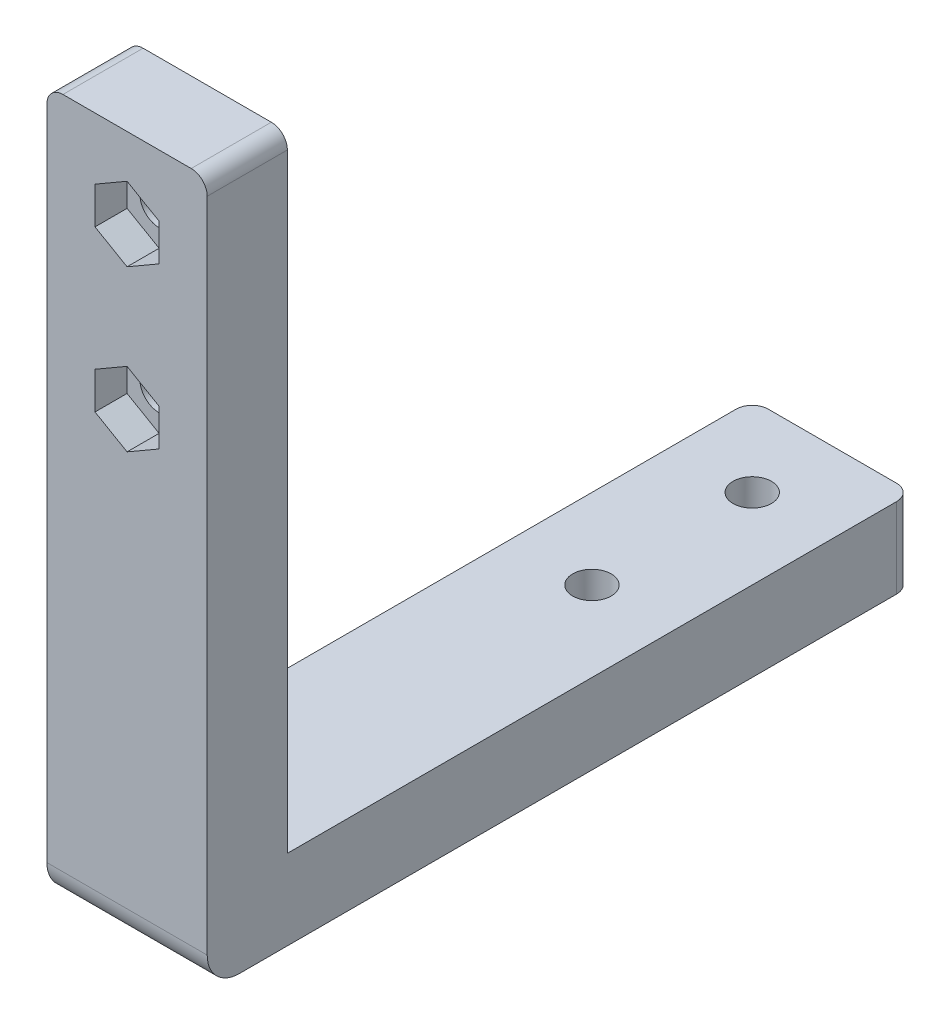
SolidWorks part; units mm, degrees
material "PEI"
ref_plane "Спереди" through (0, 0, 0) normal (0, 0, 1) x (1, 0, 0)
ref_plane "Сверху" through (0, 0, 0) normal (0, 1, 0) x (1, 0, 0)
ref_plane "Справа" through (0, 0, 0) normal (1, 0, 0) x (0, 0, -1)
sketch "Эскиз1" plane through (0, 0, 0) normal (1, 0, 0) x (0, 0, -1)
  line L0 (0, 44) -> (0, 0)
  line L1 (0, 0) -> (44, 0)
  line L2 (44, 0) -> (44, 5)
  line L3 (44, 5) -> (5, 5)
  line L4 (5, 5) -> (5, 44)
  line L5 (5, 44) -> (0, 44)
  dimension "D1" = 44
  dimension "D2" = 44
  dimension "D3" = 5
extrude "Бобышка-Вытянуть1" add sketch "Эскиз1" along normal blind 5 and the other way blind 5
sketch "Эскиз2" plane through (0, 5, 0) normal (0, 1, 0) x (1, 0, 0)
  line L1 (-10.7235, 34) -> (49989.2765, 34) construction
  line L2 (-5, 0) -> (5, 0) construction
  circle A0 centre (0, 39) radius 1.2
  circle A1 centre (0, 29) radius 1.2
  dimension "D1" = 2.4
  dimension "D2" = 29
  dimension "D3" = 5
extrude "Вырез-Вытянуть1" cut sketch "Эскиз2" against normal through all
sketch "Эскиз3" plane through (0, 0, -5) normal (0, 0, -1) x (-1, 0, 0)
  line L1 (13.3016, 34) -> (-49986.6984, 34) construction
  line L2 (5, 0) -> (-5, 0) construction
  circle A0 centre (0, 39) radius 1.2
  circle A1 centre (0, 29) radius 1.2
  dimension "D1" = 2.4
  dimension "D2" = 29
  dimension "D3" = 5
extrude "Вырез-Вытянуть2" cut sketch "Эскиз3" against normal through all
fillet "Скругление1" radius 1 4 edges at (-5, 2.5, -44) (5, 2.5, -44) (5, 44, -2.5) (-5, 44, -2.5)
fillet "Скругление2" radius 2 1 edges at (0, 0, 0)
sketch "Sketch1" plane through (0, 0, 0) normal (0, 0, -1) x (-1, 0, 0)
  line L0 (-0.2139, 34) -> (49999.7861, 34) construction
  line L1 (2, 27.8453) -> (0, 26.6906)
  line L2 (0, 41.3094) -> (-2, 40.1547)
  line L3 (-2, 40.1547) -> (-2, 37.8453)
  line L4 (-2, 37.8453) -> (0, 36.6906)
  line L5 (0, 36.6906) -> (2, 37.8453)
  line L6 (2, 37.8453) -> (2, 40.1547)
  line L7 (2, 40.1547) -> (0, 41.3094)
  line L8 (2, 30.1547) -> (2, 27.8453)
  line L9 (0, 31.3094) -> (2, 30.1547)
  line L10 (-2, 30.1547) -> (0, 31.3094)
  line L11 (-2, 27.8453) -> (-2, 30.1547)
  line L12 (0, 26.6906) -> (-2, 27.8453)
  circle A0 centre (0, 39) radius 2 construction
  circle A1 centre (0, 29) radius 2 construction
  dimension "D1" = 5
  dimension "D2" = 4
extrude "Cut-Extrude1" cut sketch "Sketch1" along normal blind 2
sketch "Sketch2" plane through (0, 0, 0) normal (0, 1, 0) x (1, 0, 0)
  line L0 (-0.1654, 34) -> (-50000.1654, 34) construction
  line L1 (2.3094, 29) -> (1.1547, 31)
  line L2 (1.1547, 31) -> (-1.1547, 31)
  line L3 (-1.1547, 31) -> (-2.3094, 29)
  line L4 (-2.3094, 29) -> (-1.1547, 27)
  line L5 (-1.1547, 27) -> (1.1547, 27)
  line L6 (1.1547, 27) -> (2.3094, 29)
  line L7 (1.1547, 41) -> (2.3094, 39)
  line L8 (-1.1547, 41) -> (1.1547, 41)
  line L9 (-2.3094, 39) -> (-1.1547, 41)
  line L10 (-1.1547, 37) -> (-2.3094, 39)
  line L11 (1.1547, 37) -> (-1.1547, 37)
  line L12 (2.3094, 39) -> (1.1547, 37)
  circle A0 centre (0, 29) radius 2 construction
  circle A1 centre (0, 39) radius 2 construction
  dimension "D1" = 5
  dimension "D2" = 4
extrude "Cut-Extrude2" cut sketch "Sketch2" along normal blind 2
